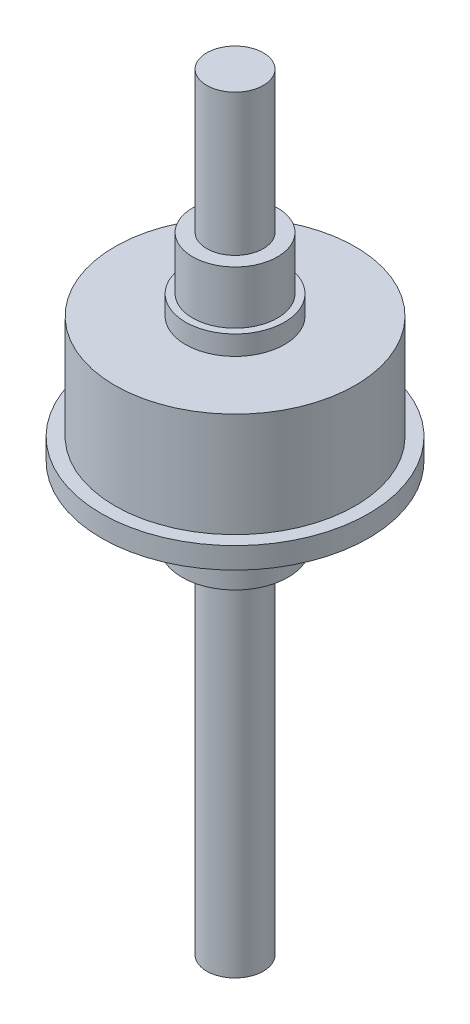
SolidWorks part; units mm, degrees
material "AISI 1035 Steel (SS)"
ref_plane "Front Plane" through (0, 0, 0) normal (0, 0, 1) x (1, 0, 0)
ref_plane "Top Plane" through (0, 0, 0) normal (0, 1, 0) x (1, 0, 0)
ref_plane "Right Plane" through (0, 0, 0) normal (1, 0, 0) x (0, 0, -1)
sketch "Sketch2" plane through (0, 0, 0) normal (0, 0, 1) x (1, 0, 0)
  line L0 (0, 40.0334) -> (0, -27.2464) construction
  line L11 (0, 0) -> (-4, 0)
  line L12 (-4, 0) -> (-4, -20)
  line L13 (-4, -20) -> (-6, -20)
  line L14 (-6, -20) -> (-6, -27.5)
  line L15 (-6, -27.5) -> (-7, -27.5)
  line L16 (-7, -27.5) -> (-7, -30.25)
  line L17 (-7, -30.25) -> (-17, -30.25)
  line L18 (-17, -30.25) -> (-17, -45.01)
  line L26 (0, -108.51) -> (0, 0)
  line L28 (-18.9, -48.01) -> (-18.9, -45.01)
  line L29 (-18.9, -45.01) -> (-17, -45.01)
  line L30 (-18.9, -48.01) -> (-10, -48.01)
  line L31 (-10, -48.01) -> (-10, -50.51)
  line L32 (-17, -45.01) -> (-17, -48.01) construction
  line L33 (-10, -50.51) -> (-7.5, -50.51)
  line L34 (-7.5, -50.51) -> (-7.5, -58.51)
  line L35 (-7.5, -58.51) -> (-4, -58.51)
  line L36 (-4, -58.51) -> (-4, -108.51)
  line L37 (-4, -108.51) -> (0, -108.51)
  dimension "D1" = 4
  dimension "D2" = 20
  dimension "D3" = 6
  dimension "D4" = 7.5
  dimension "D5" = 7
  dimension "D6" = 2.75
  dimension "D7" = 17
  dimension "D8" = 14.76
  dimension "D10" = 3
  dimension "D11" = 10
  dimension "D12" = 2.5
  dimension "D13" = 7.5
  dimension "D14" = 8
  dimension "D15" = 4
  dimension "D16" = 50
  dimension "D9" = 1.9
revolve "Revolve1" add sketch "Sketch2" angle 360 about L0
equation "\"Stator_OD\"= 68'No Tolerance given"
equation "\"A\"=18.34 'taken off spec sheet for 06808 (A)"
equation "\"Rotor_ID\"= 34'No Tolerance Given"
equation "\"back_bearing_Thickness\"= 8'randomish, thinnest off mcmaster"
equation "\"back_bearing_OD\"= 25'currently non-sense"
equation "\"Stator_Gap\"= 0.0375'+- 0.0125 (From 1.3.3.1 Kollmorgen manual)"
equation "\"Back_mount_hole\"= 1.75'To be tapped to M2 (USE LOCKTITE)"
equation "\"facePlate_Mount_Hole\"= 5.75'To be tapped to M6"
equation "\"final_shaftD\"= 8'NEMA 23 shaft diameter. Should fit with harmonic?"
equation "\"back_bearing_ID\"= 15'Random number"
equation "\"rotor_shaftD\"= \"Rotor_ID\" - (0.0185)*2'+-0.0065 (from manual)"
equation "\"back_bearing_IDOD\"= 20'Random number, OD of the inner bearing ring"
equation "\"final_shaftL\"= 50'random length. Idk"
equation "\"D1@Sketch2\" = \"final_shaftD\" / 2"
equation "\"D3@Sketch2\"=\"front_bearing_ID\"/2"
equation "\"D4@Sketch2\" = \"front_bearing_Thickness\" + 2.5"
equation "\"D5@Sketch2\"=\"front_bearing_IDOD\" / 2"
equation "\"D8@Sketch2\"=\"rotor_height\""
equation "\"front_bearing_ID\"= 12'random"
equation "\"front_bearing_OD\"= 20'random"
equation "\"front_bearing_IDOD\"= 14'random"
equation "\"front_bearing_Thickness\"= 5'randomish, thinnest off mcmaster"
equation "\"rotor_thickness\"= 2.4'measured off CAD"
equation "\"rotor_height\"= 14.76'+-0.08 taken off spec sheet for 06808 (C)"
equation "\"D11@Sketch2\"=\"back_bearing_IDOD\"/2"
equation "\"D13@Sketch2\"=\"back_bearing_ID\"/2"
equation "\"D14@Sketch2\"=\"back_bearing_Thickness\""
equation "\"D15@Sketch2\"=\"final_shaftD\"/2"
equation "\"D16@Sketch2\"=\"final_shaftL\""
equation "\"D9@Sketch2\"=\"rotor_thickness\"-0.5"
